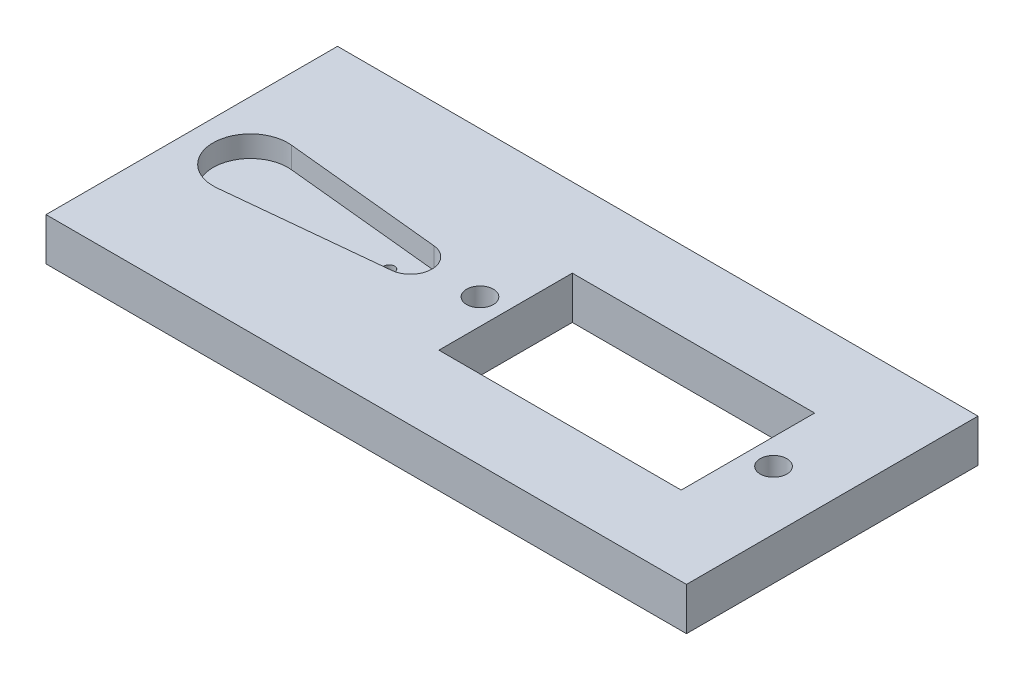
SolidWorks part; units mm, degrees
ref_plane "前视基准面" through (0, 0, 0) normal (0, 0, 1) x (1, 0, 0)
ref_plane "上视基准面" through (0, 0, 0) normal (0, 1, 0) x (1, 0, 0)
ref_plane "右视基准面" through (0, 0, 0) normal (1, 0, 0) x (0, 0, -1)
other "Configuration Table"
sketch "草图1" plane through (0, 0, 0) normal (0, 1, 0) x (1, 0, 0)
  line L0 (-24.15, 3.4825) -> (-9.3, 1.99)
  line L1 (-30, 13.6546) -> (30, 13.6546)
  line L2 (-30, 13.6546) -> (-30, -13.6546)
  line L3 (-30, -13.6546) -> (30, -13.6546)
  line L4 (30, 13.6546) -> (30, -13.6546)
  line L5 (-30, 13.6546) -> (30, -13.6546) construction
  line L6 (-30, -13.6546) -> (30, 13.6546) construction
  line L7 (-0.6, 6.25) -> (22.1, 6.25)
  line L8 (-0.6, 6.25) -> (-0.6, -6.25)
  line L9 (-0.6, -6.25) -> (22.1, -6.25)
  line L10 (22.1, 6.25) -> (22.1, -6.25)
  line L11 (-0.6, 6.25) -> (22.1, -6.25) construction
  line L12 (-0.6, -6.25) -> (22.1, 6.25) construction
  line L13 (-24.15, -3.4825) -> (-9.3, -1.99)
  line L14 (10.75, -8.5449) -> (10.75, 8.614) construction
  circle A0 centre (-24.5, 0) radius 3.5
  circle A1 centre (-11.5, 0) radius 0.5
  circle A2 centre (-9.5, 0) radius 2
  circle A3 centre (-3, 0) radius 1.25
  circle A4 centre (24.5, 0) radius 1.25
  point P0 (0, 0)
  point P12 (10.75, 0)
  point P21 (-30, 0)
  point P28 (23.2449, -8.5449)
  point P29 (23.2684, 8.614)
  point P30 (0, 0)
  point P31 (30, 0)
  dimension "D1" = 7
  dimension "D2" = 4
  dimension "D3" = 1
  dimension "D5" = 13
  dimension "D6" = 5.5
  dimension "D8" = 12.5
  dimension "D9" = 17.1589
  dimension "D10" = 27.5
  dimension "D11" = 5.5
  dimension "D12" = 2.5
  dimension "D13" = 27.3092
  dimension "D4" = 15
  dimension "D7" = 22.7
  dimension "D14" = 60
extrude "凸台-拉伸2" add sketch "草图1" along normal blind 4 contours L4 L1 L2 L3 A4 A3 A2 L13 A0 L0 L7 L10 L9 L8 region at (-0.9183, 0, 0)
extrude "凸台-拉伸3" add sketch "草图1<4>" along normal blind 2 contours A0 | A2 L0 A0 L13 A1 | A2 A1 region at (-16.7322, 0, 0) region at (-24.5, 0, 0) region at (-9.4458, 0, 0)
sketch "草图1<4>" plane through (0, 0, 0) normal (0, 1, 0) x (1, 0, 0) same geometry as "草图1"
